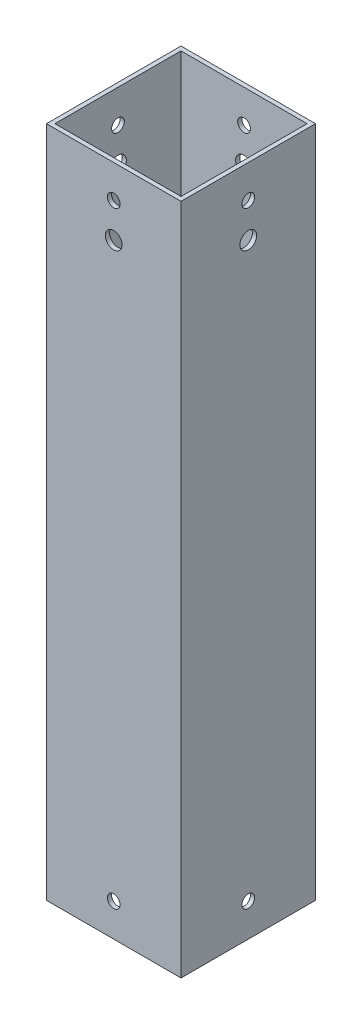
SolidWorks part; units mm, degrees
material "6061 Alloy"
ref_plane "Front Plane" through (0, 0, 0) normal (0, 0, 1) x (1, 0, 0)
ref_plane "Top Plane" through (0, 0, 0) normal (0, 1, 0) x (1, 0, 0)
ref_plane "Right Plane" through (0, 0, 0) normal (1, 0, 0) x (0, 0, -1)
sketch "Sketch1" plane through (0, 0, 0) normal (0, 1, 0) x (1, 0, 0)
  line L1 (-23.8125, 23.8125) -> (23.8125, 23.8125)
  line L2 (-23.8125, 23.8125) -> (-23.8125, -23.8125)
  line L3 (-23.8125, -23.8125) -> (23.8125, -23.8125)
  line L4 (23.8125, 23.8125) -> (23.8125, -23.8125)
  line L5 (-25.4, 25.4) -> (25.4, 25.4)
  line L6 (-25.4, 25.4) -> (-25.4, -25.4)
  line L7 (-25.4, -25.4) -> (25.4, -25.4)
  line L8 (25.4, 25.4) -> (25.4, -25.4)
  point P2 (-25.4, 0)
  point P11 (-23.8125, 0)
  point P12 (0, 23.8125)
  point P13 (0, 25.4)
  dimension "D1" = 47.625
  dimension "1.95" = 47.625
  dimension "2.05" = 50.8
  dimension "D2" = 50.8
extrude "Boss-Extrude1" add sketch "Sketch1" along normal blind 254
ref_plane "Plane1" through (0, 152.4, 0) normal (0, 1, 0) x (1, 0, 0)
sketch "Sketch4" plane through (-23.8125, 0, 0) normal (1, 0, 0) x (0, 0, -1)
  line L0 (-25.4, 254) -> (25.4, 254) construction
  line L1 (25.4, 254) -> (25.4, 0) construction
  circle A0 centre (0, 241.5876) radius 2.4
  dimension "D1" = 4.8
  dimension "D2" = 12.4124
  dimension "D3" = 25.4
extrude "Cut-Extrude1" cut sketch "Sketch4" along normal through all both and the other way through all
sketch "Sketch5" plane through (0, 0, -25.4) normal (0, 0, -1) x (-1, 0, 0)
  line L0 (-25.4, 254) -> (25.4, 254) construction
  line L1 (25.4, 254) -> (25.4, 0) construction
  circle A0 centre (0, 241.5876) radius 2.4
  dimension "D1" = 4.8
  dimension "D2" = 12.4124
  dimension "D3" = 25.4
extrude "Cut-Extrude2" cut sketch "Sketch5" against normal through all
sketch "Sketch6" plane through (25.4, 0, 0) normal (1, 0, 0) x (0, 0, -1)
  line L0 (-25.4, 0) -> (25.4, 0) construction
  line L1 (25.4, 254) -> (25.4, 0) construction
  circle A0 centre (0, 12.4124) radius 2.4
  dimension "D1" = 12.4124
  dimension "D2" = 4.8
  dimension "D3" = 25.4
extrude "Cut-Extrude3" cut sketch "Sketch6" against normal through all both and the other way through all
sketch "Sketch7" plane through (0, 0, -25.4) normal (0, 0, -1) x (-1, 0, 0)
  line L0 (-25.4, 0) -> (25.4, 0) construction
  circle A0 centre (0, 12.4124) radius 2.4
  dimension "D1" = 4.8
  dimension "D2" = 12.4124
  dimension "D3" = 25.4
extrude "Cut-Extrude4" cut sketch "Sketch7" against normal through all both
sketch "Sketch8" plane through (0, 0, -25.4) normal (0, 0, -1) x (-1, 0, 0)
  line L0 (-25.4, 254) -> (25.4, 254) construction
  line L1 (-25.4, 254) -> (-25.4, 0) construction
  circle A0 centre (0, 228.6) radius 3.175
  dimension "D1" = 6.35
  dimension "D2" = 25.4
  dimension "D3" = 25.4
extrude "Cut-Extrude5" cut sketch "Sketch8" against normal through all both and the other way through all
sketch "Sketch9" plane through (25.4, 0, 0) normal (1, 0, 0) x (0, 0, -1)
  line L0 (-25.4, 254) -> (25.4, 254) construction
  line L1 (-25.4, 254) -> (-25.4, 0) construction
  circle A0 centre (0, 228.6) radius 3.175
  dimension "D1" = 6.35
  dimension "D2" = 25.4
  dimension "D3" = 25.4
extrude "Cut-Extrude6" cut sketch "Sketch9" against normal through all both
equation "\"1.95@Sketch1\"=2-(1/8)"
equation "\"D1@Sketch1\"=\"1.95@Sketch1\""
